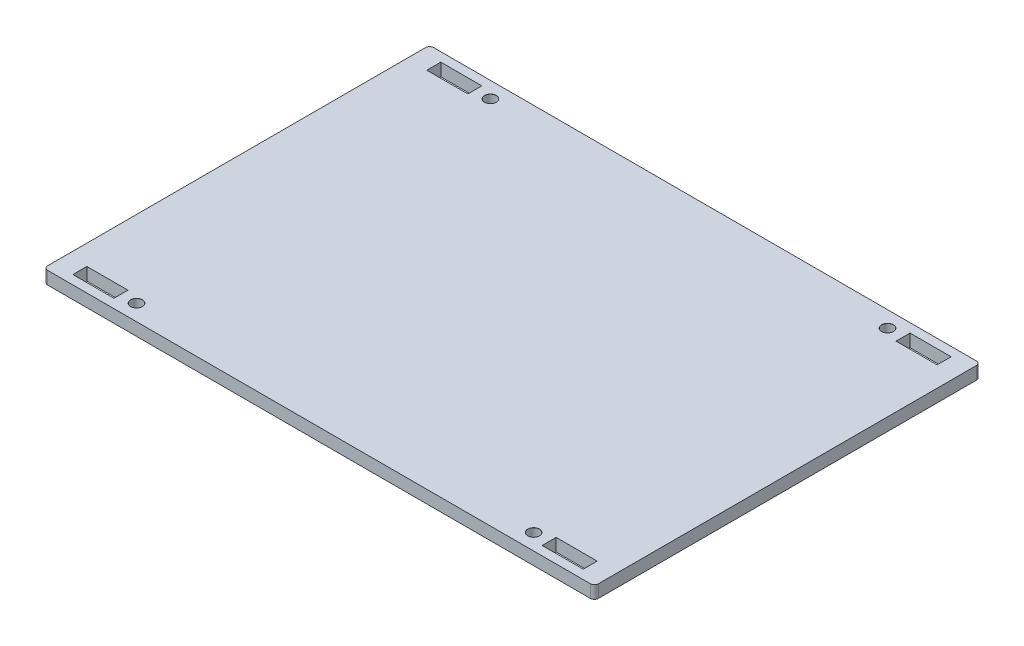
SolidWorks part; units mm, degrees
material "MDF"
ref_plane "Front Plane" through (0, 0, 0) normal (0, 0, 1) x (1, 0, 0)
ref_plane "Top Plane" through (0, 0, 0) normal (0, 1, 0) x (1, 0, 0)
ref_plane "Right Plane" through (0, 0, 0) normal (1, 0, 0) x (0, 0, -1)
sketch "Sketch1" plane through (0, 0, 0) normal (0, 1, 0) x (1, 0, 0)
  line L1 (-68.745, -48.1725) -> (68.745, -48.1725)
  line L2 (-68.745, -48.1725) -> (-68.745, 48.1725)
  line L3 (-68.745, 48.1725) -> (68.745, 48.1725)
  line L4 (68.745, -48.1725) -> (68.745, 48.1725)
  line L5 (-68.745, -48.1725) -> (68.745, 48.1725) construction
  line L6 (-68.745, 48.1725) -> (68.745, -48.1725) construction
  line L7 (-68.745, -44.1725) -> (68.745, -44.1725) construction
  line L8 (-68.745, -44.1725) -> (-68.745, 44.1725)
  line L9 (-68.745, 44.1725) -> (68.745, 44.1725) construction
  line L10 (68.745, -44.1725) -> (68.745, 44.1725)
  line L11 (-68.745, -44.1725) -> (68.745, 44.1725) construction
  line L12 (-68.745, 44.1725) -> (68.745, -44.1725) construction
  line L13 (-63.695, 42.4262) -> (-53.445, 42.4262)
  line L14 (-63.695, 42.4262) -> (-63.695, 45.9187)
  line L15 (-63.695, 45.9187) -> (-53.445, 45.9187)
  line L16 (-53.445, 42.4262) -> (-53.445, 45.9187)
  line L17 (-63.695, 42.4262) -> (-53.445, 45.9187) construction
  line L18 (-63.695, 45.9187) -> (-53.445, 42.4262) construction
  circle A0 centre (-49.57, 44.1725) radius 2.5
  point P0 (0, 0)
  point P6 (0, 0)
  point P11 (-58.57, 44.1725)
  dimension "D8" = 5
  dimension "D1" = 88.345
  dimension "D2" = 137.49
  dimension "D3" = 4
  dimension "D4" = 10.175
  dimension "D5" = 10.25
  dimension "D6" = 3.4925
  dimension "D7" = 19.175
extrude "Boss-Extrude1" add sketch "Sketch1" along normal blind 3.175 contours L1 L4 L3 L2 A0 L16 L13 L14 L15 | L13 L16 L15 L14 | A0 region at (0.2327, 0, 0.1856) region at (-58.57, 0, -44.1725) region at (-49.57, 0, -44.1725)
extrude "Cut-Extrude1" cut sketch "Sketch1<3>" against normal through all both and the other way through all contours L13 L16 L15 L14 region at (-58.57, 0, -44.1725)
sketch "Sketch1<3>" plane through (0, 0, 0) normal (0, 1, 0) x (1, 0, 0) same geometry as "Sketch1"
sketch "Sketch2" plane through (0, 3.175, 0) normal (0, 1, 0) x (1, 0, 0)
  point P0 (-49.57, 44.1725)
hole_wizard "M2.5 Clearance Hole1" positions "Sketch2" profile "Sketch3" hole size "M2.5" standard "ANSI Metric" end condition through all
sketch "Sketch3" plane through (-49.57, 3.175, -44.1725) normal (1, 0, 0) x (0, 0, 1)
  line L0 (0, 0) -> (0, 3.175)
  line L1 (0, 3.175) -> (1.45, 3.175)
  line L2 (1.45, 3.175) -> (1.45, 0.021)
  line L3 (1.45, 0.021) -> (1.475, 0)
  line L5 (1.475, 0) -> (0, 0)
  line L6 (-1.45, 0.021) -> (-1.475, 0) construction
  line L11 (0, -6.35) -> (0, 107.95) construction
  dimension "Thru Hole Dia." = 2.9
  dimension "Thru Hole Depth" = 3.175
  dimension "Near C'Sink Dia." = 2.95
  dimension "Near C'Sink Angle" = 100
mirror "Mirror1" about plane through (0, 0, 0) normal (1, 0, 0) of "M2.5 Clearance Hole1", "Cut-Extrude1" second plane through (0, 0, 0) second plane normal (0, 0, 1)
fillet "Fillet1" radius 1 4 edges at (68.745, 1.5875, -48.1725) (68.745, 1.5875, 48.1725) (-68.745, 1.5875, 48.1725) (-68.745, 1.5875, -48.1725)
